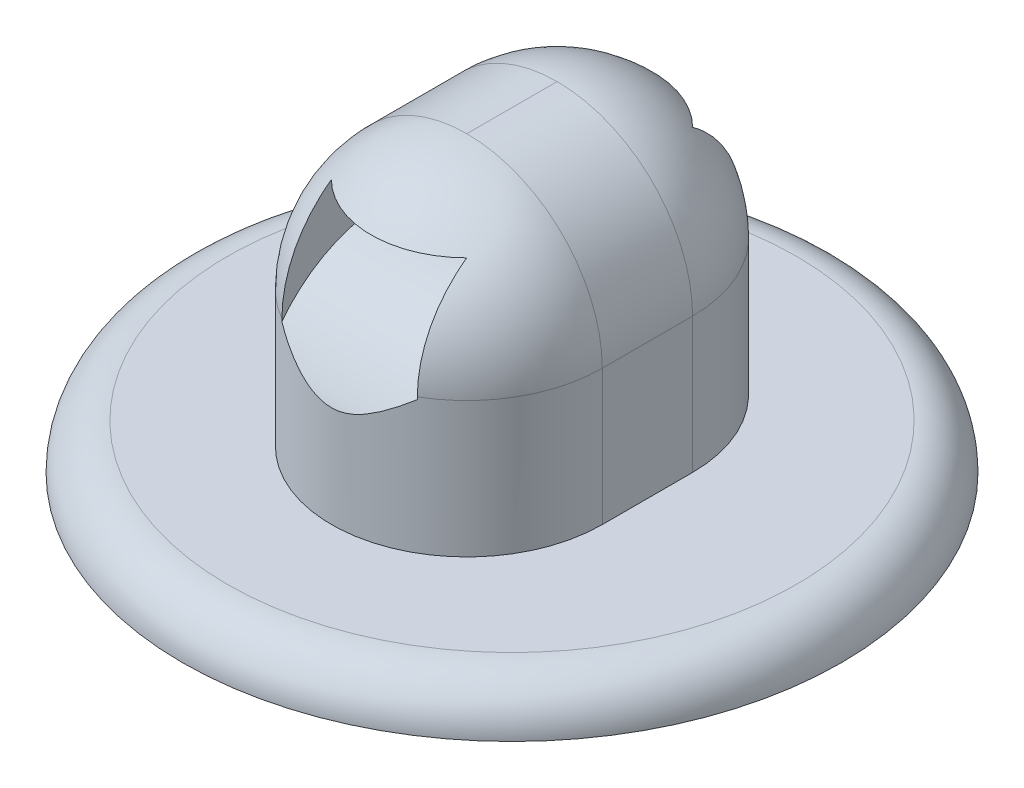
SolidWorks part; units mm, degrees
ref_plane "Front Plane" through (0, 0, 0) normal (0, 0, 1) x (1, 0, 0)
ref_plane "Top Plane" through (0, 0, 0) normal (0, 1, 0) x (1, 0, 0)
ref_plane "Right Plane" through (0, 0, 0) normal (1, 0, 0) x (0, 0, -1)
sketch "Sketch1" plane through (0, 0, 0) normal (0, 1, 0) x (1, 0, 0)
  circle A0 centre (0, 0) radius 7.3
  dimension "D1" = 14.6
extrude "Boss-Extrude1" add sketch "Sketch1" along normal blind 1 contours A0
sketch "Sketch2" plane through (0, 1, 0) normal (0, 1, 0) x (1, 0, 0)
  line L0 (0, 1) -> (0, -1) construction
  line L1 (3, 1) -> (3, -1)
  line L2 (-3, 1) -> (-3, -1)
  arc A0 (3, 1) -> (-3, 1) centre (0, 1) ccw
  arc A1 (-3, -1) -> (3, -1) centre (0, -1) ccw
  circle A3 centre (0, 0) radius 7.3 construction
  point P3 (0, 0)
  point P8 (0, 0)
  point P11 (0, 0)
  point P12 (0, -1.8443)
  dimension "D2" = 3
  dimension "D1" = 2
extrude "Boss-Extrude2" add sketch "Sketch2" along normal blind 6 contours A0 L2 A1 L1
fillet "Fillet1" radius 3 4 edges at (-3, 7, 0) (0, 7, -4) (3, 7, 0) (0, 7, 4)
fillet "Fillet2" radius 1 1 edges at (0, 1, 7.3)
sketch "Sketch3" plane through (-3, 0, 0) normal (-1, 0, 0) x (0, 0, 1)
  line L0 (-4, 6.1195) -> (4, 6.1195)
  line L1 (-4, 6.1195) -> (-4, 3.2426)
  line L2 (-1.2182, 5.1195) -> (1.2182, 5.1195)
  line L3 (4, 6.1195) -> (4, 3.2426)
  line L4 (4, 1) -> (4, 4) construction
  arc A2 (-4, 3.2426) -> (-1.2182, 5.1195) centre (-1.2182, 2.1195) cw
  arc A3 (1.2182, 5.1195) -> (4, 3.2426) centre (1.2182, 2.1195) cw
  point P0 (-4, 4.738)
  point P1 (0, 0)
  dimension "D1" = 8
  dimension "D2" = 3
  dimension "D3" = 1
extrude "Cut-Extrude1" cut sketch "Sketch3" against normal blind 3 from offset 1.5 offset against normal yes
